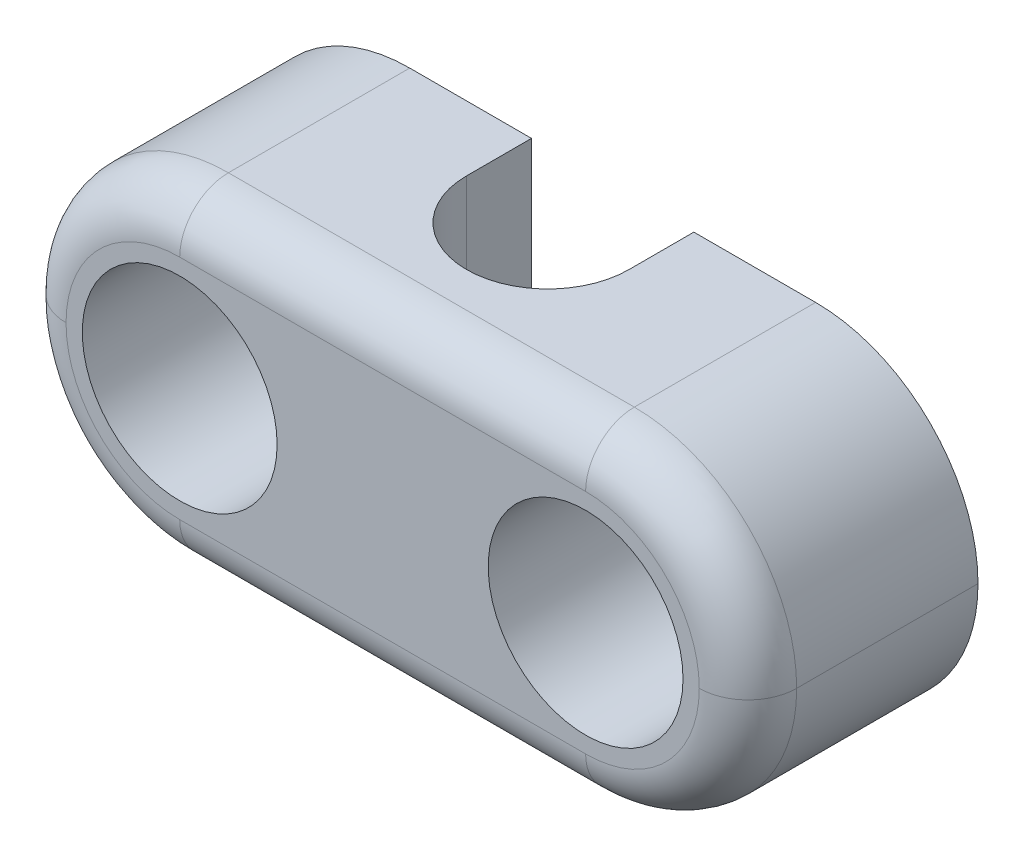
SolidWorks part; units mm, degrees
material "Plain Carbon Steel"
ref_plane "Front Plane" through (0, 0, 0) normal (0, 0, 1) x (1, 0, 0)
ref_plane "Top Plane" through (0, 0, 0) normal (0, 1, 0) x (1, 0, 0)
ref_plane "Right Plane" through (0, 0, 0) normal (1, 0, 0) x (0, 0, -1)
sketch "Sketch2" plane through (0, 0, 0) normal (0, 0, 1) x (1, 0, 0)
  line L1 (-22.5, -10) -> (22.5, -10)
  line L2 (-22.5, -10) -> (-22.5, 10)
  line L3 (-22.5, 10) -> (22.5, 10)
  line L4 (22.5, -10) -> (22.5, 10)
  line L5 (-22.5, -10) -> (22.5, 10) construction
  line L6 (-22.5, 10) -> (22.5, -10) construction
  point P0 (0, 0)
  dimension "D1" = 45
  dimension "D2" = 20
extrude "Boss-Extrude2" add sketch "Sketch2" along normal blind 14.1679
fillet "Fillet1" radius 10 4 edges at (22.5, 10, 7.0839) (22.5, -10, 7.0839) (-22.5, 10, 7.0839) (-22.5, -10, 7.0839)
sketch "Sketch3" plane through (0, -10, 0) normal (0, -1, 0) x (1, 0, 0)
  line L0 (0, 0) -> (0, 4) construction
  line L1 (-12.5, 0) -> (12.5, 0) construction
  line L2 (-5, 0) -> (-5, 4)
  line L3 (5, 0) -> (5, 4)
  line L5 (-12.5, 14.1679) -> (12.5, 14.1679) construction
  arc A0 (-5, 0) -> (5, 0) centre (0, 0) ccw
  arc A1 (5, 4) -> (-5, 4) centre (0, 4) ccw
  point P4 (0, 2)
  dimension "D2" = 9
  dimension "D3" = 5.1679
  dimension "D1" = 10
extrude "Cut-Extrude1" cut sketch "Sketch3" against normal blind 22
hole_wizard "CBORE for M5 Hex Head Bolt1" positions "Sketch8" profile "Sketch7" counterbore size "M5" standard "ANSI Metric" end condition through all
sketch "Sketch8" plane through (0, 0, 14.1679) normal (0, 0, 1) x (1, 0, 0)
  point P0 (-12.5, 0)
  point P2 (12.5, 0)
  dimension "D1" = 25
  dimension "D2" = 10
  dimension "D3" = 10
sketch "Sketch7" plane through (-12.5, 0, 14.1679) normal (1, 0, 0) x (0, -1, 0)
  line L0 (0, 0) -> (0, 14.1679)
  line L1 (0, 14.1679) -> (2.75, 14.1679)
  line L3 (2.75, 14.1679) -> (2.75, 10)
  line L4 (2.75, 10) -> (6, 10)
  line L5 (6, 10) -> (6, 0)
  line L7 (6, 0) -> (0, 0)
  line L11 (0, -6.35) -> (0, 107.95) construction
  dimension "Thru Hole Dia." = 5.5
  dimension "Thru Hole Depth" = 14.1679
  dimension "C'Bore Dia." = 12
  dimension "C'Bore Depth" = 10
fillet "Fillet2" radius 3 6 edges at (-19.5711, -7.0711, 14.1679) (-19.5711, 7.0711, 14.1679) (0, 10, 14.1679) (19.5711, 7.0711, 14.1679) (19.5711, -7.0711, 14.1679) (0, -10, 14.1679)
